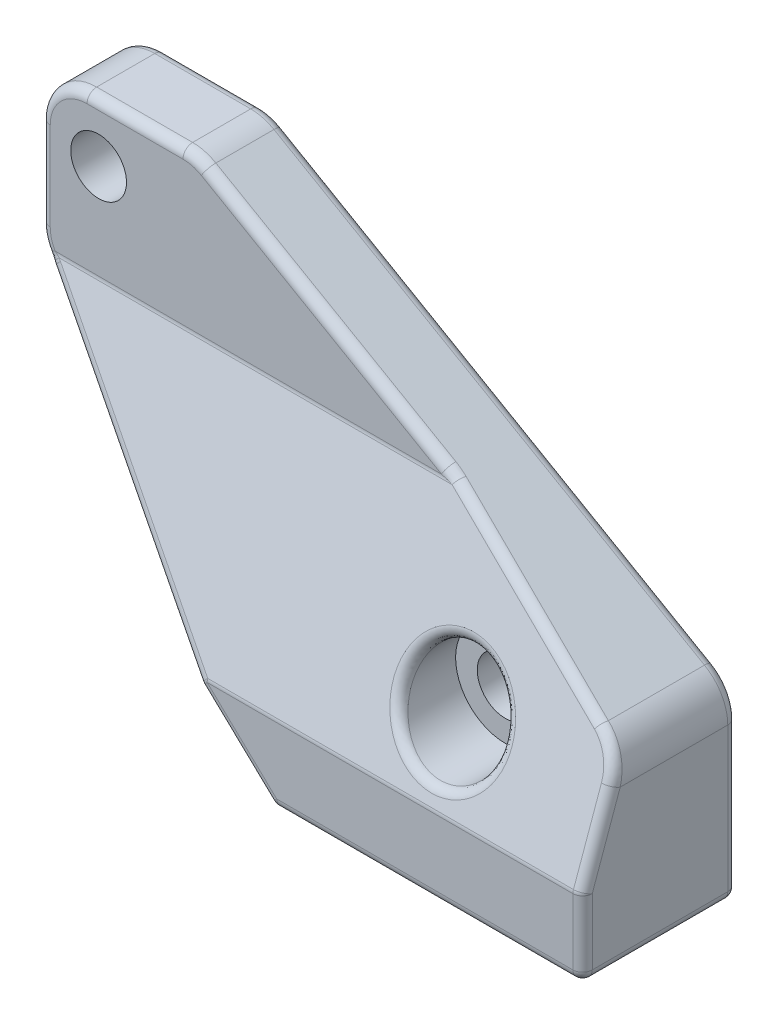
SolidWorks part; units mm, degrees
ref_plane "Front Plane" through (0, 0, 0) normal (0, 0, 1) x (1, 0, 0)
ref_plane "Top Plane" through (0, 0, 0) normal (0, 1, 0) x (1, 0, 0)
ref_plane "Right Plane" through (0, 0, 0) normal (1, 0, 0) x (0, 0, -1)
sketch "Sketch8" plane through (0, 0, 0) normal (0, 0, 1) x (1, 0, 0)
  line L0 (0, 0) -> (-25.4, 0)
  line L3 (-50.8, 36.83) -> (-38.1, 36.83)
  line L4 (-38.1, 36.83) -> (0, 14.833)
  line L5 (0, 14.833) -> (0, 0)
  line L6 (-50.8, 36.83) -> (-50.8, 24.13)
  line L7 (-50.8, 36.83) -> (-50.8, -7.62) construction
  line L8 (-50.8, 24.13) -> (-25.4, 0)
  circle A0 centre (-12.7, 11.8269) radius 2.286 construction
  circle A1 centre (-46.0375, 32.0675) radius 2.286 construction
  circle A2 centre (-12.7, 11.8269) radius 2.286
  circle A3 centre (-46.0375, 32.0675) radius 2.286
  dimension "D1" = 12.7
  dimension "D2" = 12.7
  dimension "D3" = 150
  dimension "D4" = 25.4
extrude "Boss-Extrude1" add sketch "Sketch8" along normal blind 12.7
sketch "Sketch9" plane through (0, 0, 0) normal (0, -1, 0) x (1, 0, 0)
  line L0 (0, 12.7) -> (0, 0) construction
  line L4 (-25.4, 12.7) -> (0, 12.7) construction
  circle A0 centre (-6.35, 6.35) radius 1.905
  circle A1 centre (-19.05, 6.35) radius 1.905
  dimension "D2" = 6.35
  dimension "D4" = 3.81
  dimension "D1" = 6.35
  dimension "D5" = 12.7
  dimension "D3" = 2
extrude "Cut-Extrude4" cut sketch "Sketch9" against normal blind 15.875
sketch "Sketch10" plane through (-50.8, 0, 0) normal (-1, 0, 0) x (0, 0, 1)
  line L0 (6.35, 36.83) -> (6.35, 24.13)
  line L1 (12.7, 36.83) -> (0, 36.83) construction
  line L2 (6.35, 24.13) -> (12.7, 6.35)
  line L3 (12.7, 24.13) -> (12.7, 0) construction
  line L4 (12.7, 6.35) -> (12.7, 36.83)
  line L5 (12.7, 36.83) -> (12.7, 24.13) construction
  line L6 (12.7, 36.83) -> (6.35, 36.83)
  line L7 (12.7, 0) -> (0, 0) construction
  dimension "D1" = 12.7
  dimension "D2" = 6.35
extrude "Cut-Extrude5" cut sketch "Sketch10" against normal through all
sketch "Sketch11" plane through (0, 0, 12.7) normal (0, 0, 1) x (1, 0, 0)
  circle A0 centre (-12.7, 11.8269) radius 4.064
  dimension "D1" = 8.128
extrude "Cut-Extrude6" cut sketch "Sketch11" against normal offset from surface (6.35 mm away) 6.35 up to face at (-10.414, 11.8269, 0)
fillet "Fillet1" radius 3.81 4 edges at (-50.8, 24.13, 3.175) (-50.8, 36.83, 3.175) (-38.1, 36.83, 3.175) (0, 14.833, 4.8352)
fillet "Fillet2" radius 0.7937 29 edges at (-9.004, 20.0314, 7.8138) (-0.5104, 14.5383, 9.7756) (-0.5104, 14.5383, 0) (-19.5604, 26.1262, 0) (-38.1348, 36.7002, 0) (-43.0554, 36.83, 0) (-49.6841, 35.7141, 0) (-50.8, 29.3928, 0) (-50.491, 24.2627, 0) (-50.0745, 23.5291, 6.5646) (-26.6594, 30.2248, 6.35) (-38.1348, 36.7002, 6.35) (-43.0554, 36.83, 6.35) (-49.6841, 35.7141, 6.35) (-50.7066, 24.9273, 6.35) (0, 0, 6.35) (0, 3.175, 12.7) (0, 9.4916, 11.578) (0, 6.3166, 0) (-28.7421, 3.175, 12.7) (-25.4, 0, 6.35) (-37.5071, 11.5017, 0) (-40.8492, 14.6767, 9.7262) (-12.7, 0, 12.7) (-12.7, 0, 0) (-16.0421, 6.35, 12.7) (-33.267, 24.13, 6.35) (-50.8, 29.3928, 6.35) (-12.7, 7.7629, 12.1954)
